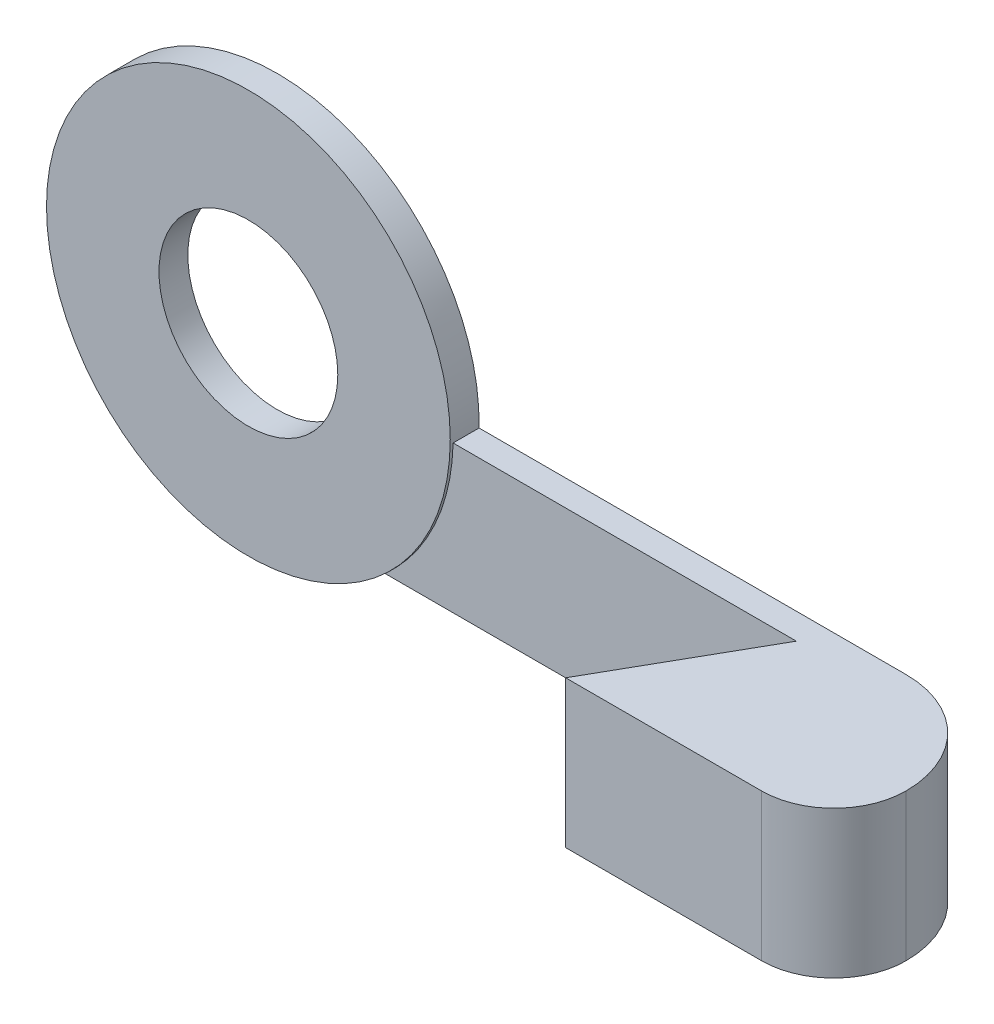
SolidWorks part; units mm, degrees
ref_plane "Front" through (0, 0, 0) normal (0, 0, 1) x (1, 0, 0)
ref_plane "Top" through (0, 0, 0) normal (0, 1, 0) x (1, 0, 0)
ref_plane "Right" through (0, 0, 0) normal (1, 0, 0) x (0, 0, -1)
sketch "Sketch3" plane through (0, 0, 0) normal (0, 1, 0) x (1, 0, 0)
  line L0 (0, -2.5) -> (-3.9, -2.5)
  line L1 (-3.9, -2.5) -> (-3.9, 3.5)
  line L2 (-3.9, 3.5) -> (-1, 3.5)
  arc A0 (2.5, 0) -> (0, -2.5) centre (0, 0) cw
  arc A1 (-1, 3.5) -> (2.5, 0) centre (-1, 0) cw
  dimension "D1" = 2.5
  dimension "D2" = 6.4
  dimension "D3" = 6
extrude "Boss-Extrude1" add sketch "Sketch3" along normal blind 5.1
sketch "Sketch4" plane through (-3.9, 0, 0) normal (-1, 0, 0) x (0, 0, 1)
  line L1 (-3.5, 5.1) -> (-2.6, 5.1)
  line L2 (-3.5, 5.1) -> (-3.5, 0)
  line L3 (-3.5, 0) -> (-2.6, 0)
  line L4 (-2.6, 5.1) -> (-2.6, 0)
  dimension "D1" = 0.9
extrude "Boss-Extrude2" add sketch "Sketch4" along normal blind 18.9
sketch "Sketch5" plane through (0, 0, -3.5) normal (0, 0, -1) x (-1, 0, 0)
  line L0 (22.8, 5.1) -> (22.8, 0) construction
  line L2 (1, 5.1) -> (22.8, 5.1) construction
  circle A0 centre (22.8, 5.25) radius 7
  dimension "D2" = 14
  dimension "D1" = 0.15
extrude "Boss-Extrude3" add sketch "Sketch5" against normal blind 1
sketch "Sketch6" plane through (0, 0, -2.6) normal (0, 0, 1) x (1, 0, 0)
  circle A0 centre (-22.8, 5.25) radius 3.1
  circle A1 centre (-22.8, 5.25) radius 7 construction
  dimension "D1" = 6.2
extrude "Cut-Extrude1" cut sketch "Sketch6" against normal through all both and the other way through all
sketch "Sketch7" plane through (0, 0, 0) normal (0, -1, 0) x (1, 0, 0)
  line L3 (-3.9, -2.6) -> (-3.9, 2.5)
  line L4 (-3.9, 2.5) -> (-6.8, 2.5)
  line L5 (-6.8, 2.5) -> (-3.9, -2.6)
  dimension "D1" = 2.9
extrude "Boss-Extrude4" add sketch "Sketch7" against normal up to surface (5.1 mm away) up to face at (-5.2372, 5.1, -1.0582)
